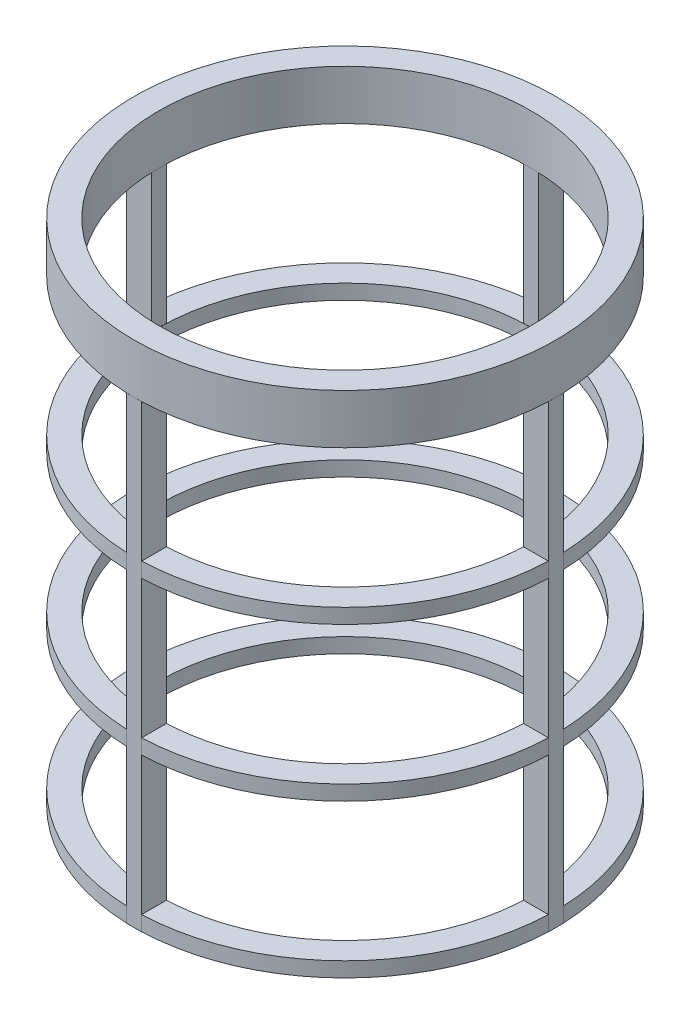
SolidWorks part; units mm, degrees
ref_plane "Front Plane" through (0, 0, 0) normal (0, 0, 1) x (1, 0, 0)
ref_plane "Top Plane" through (0, 0, 0) normal (0, 1, 0) x (1, 0, 0)
ref_plane "Right Plane" through (0, 0, 0) normal (1, 0, 0) x (0, 0, -1)
sketch "Sketch1" plane through (0, 0, 0) normal (1, 0, 0) x (0, 0, -1)
  line L0 (0, 0) -> (0, -12.7)
  line L1 (0, -12.7) -> (6.35, -12.7)
  line L2 (6.35, -12.7) -> (6.35, 0)
  line L3 (6.35, 0) -> (0, 0)
  line L4 (0, -12.7) -> (0, -130.175)
  line L5 (6.35, -12.7) -> (6.35, -130.175)
  line L6 (0, -130.175) -> (107.95, -130.175) construction
  line L7 (53.975, -130.175) -> (53.975, -184.15) construction
  line L8 (107.95, -12.7) -> (107.95, -130.175)
  line L9 (101.6, -12.7) -> (101.6, -130.175)
  line L10 (107.95, -12.7) -> (101.6, -12.7)
  arc A0 (0, -130.175) -> (107.95, -130.175) centre (53.975, -130.175) ccw
  arc A1 (0, -130.175) -> (107.95, -130.175) centre (53.975, -130.175) ccw
  arc A2 (6.35, -130.175) -> (101.6, -130.175) centre (53.975, -130.175) ccw
  point P3 (53.975, -184.15)
  dimension "D1" = 6.35
  dimension "D2" = 12.7
  dimension "D3" = 184.15
  dimension "D4" = 107.95
  dimension "D5" = 0
  dimension "D6" = 6.35
revolve "Revolve6" add sketch "Sketch1" angle 360 about L7 region at (0, -6.35, -3.175)
extrude "Boss-Extrude1" add sketch "Sketch1<6>" along normal blind 1.905 and the other way blind 1.905 contours A2 L5 L1 L4 A0 L8 L10 L9 region at (0, -14.726, -3.175)
sketch "Sketch1<6>" plane through (0, 0, 0) normal (1, 0, 0) x (0, 0, -1) same geometry as "Sketch1"
pattern_circular "CirPattern1" count 2 every 90 about axis through (0, -130.175, -53.975) along (0, -1, 0) of "Boss-Extrude1"
ref_plane "Plane1" through (0, -130.175, 0) normal (0, -1, 0) x (-1, 0, 0)
sketch "Sketch2" plane through (0, -130.175, 0) normal (0, -1, 0) x (-1, 0, 0)
  circle A0 centre (0, 53.975) radius 53.975
  circle A1 centre (0, 53.975) radius 47.625
  arc A2 (47.625, 53.975) -> (0, 101.6) centre (0, 53.975) ccw construction
extrude "Boss-Extrude2" add sketch "Sketch2" against normal blind 3.81
pattern_linear "LPattern1" count 3 spacing 39.1583 along (0, 1, 0) of "Boss-Extrude2"
sketch "Sketch4" plane through (0, -130.175, 0) normal (0, -1, 0) x (1, 0, 0)
  circle A0 centre (0, -53.975) radius 60.96
  dimension "D1" = 121.92
extrude "Cut-Extrude1" cut sketch "Sketch4" along normal blind 66.04
